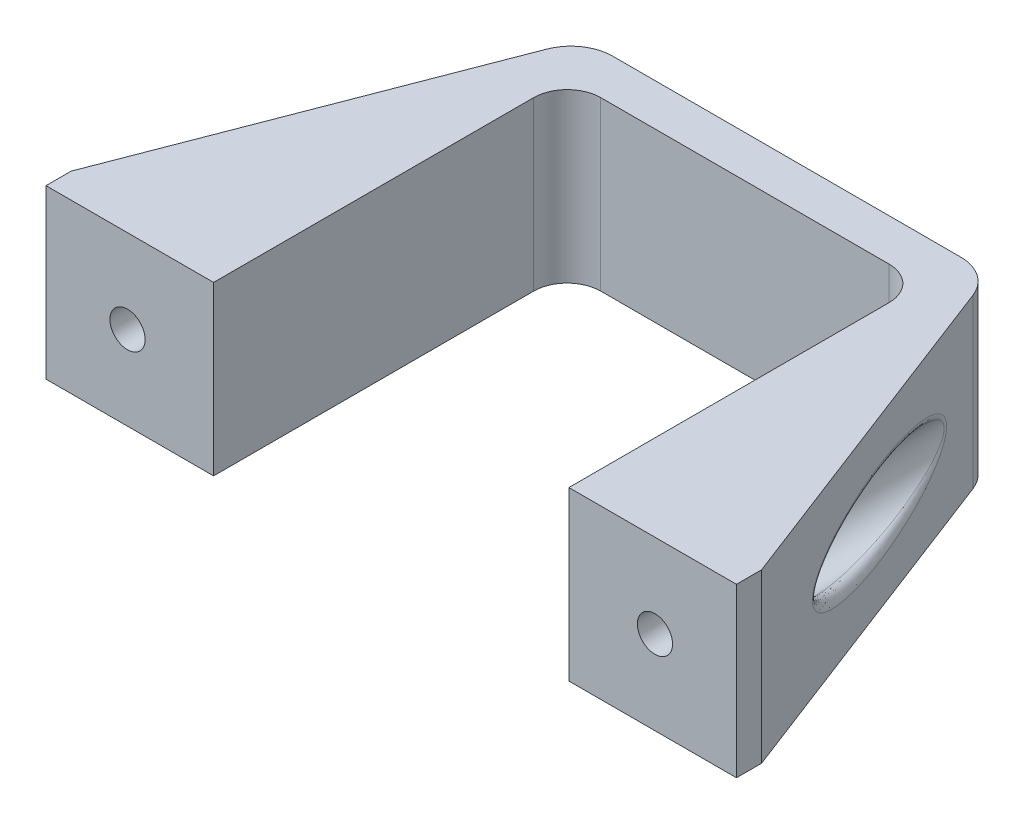
SolidWorks part; units mm, degrees
ref_plane "前视基准面" through (0, 0, 0) normal (0, 0, 1) x (1, 0, 0)
ref_plane "上视基准面" through (0, 0, 0) normal (0, 1, 0) x (1, 0, 0)
ref_plane "右视基准面" through (0, 0, 0) normal (1, 0, 0) x (0, 0, -1)
other "Configuration Table"
sketch "草图1" plane through (0, 0, 0) normal (0, 1, 0) x (1, 0, 0)
  line L0 (-21.2, 6.0133) -> (-21.2, 0)
  line L1 (-21.2, 42.2) -> (21.2, 42.2)
  line L2 (21.2, 42.2) -> (21.2, 6.0133)
  line L4 (41.2, 3) -> (41.2, 0)
  line L5 (41.2, 0) -> (21.2, 0)
  line L7 (0, 42.2) -> (0, 47.2)
  line L8 (-24.2, 47.2) -> (24.2, 47.2)
  line L10 (21.2, 6.0133) -> (21.2, 0)
  line L12 (-41.2, 0) -> (-21.2, 0)
  line L13 (-41.2, 3) -> (-41.2, 0)
  line L15 (-21.2, 42.2) -> (-21.2, 6.0133)
  line L16 (-24.2, 47.2) -> (-41.2, 3)
  line L17 (24.2, 47.2) -> (41.2, 3)
  dimension "D1" = 21.2
  dimension "D2" = 42.2
  dimension "D3" = 20
  dimension "D4" = 3
  dimension "D5" = 5
extrude "凸台-拉伸1" add sketch "草图1" along normal blind 20 contours L8 L17 L4 L5 L10 L2 L1 L15 L0 L12 L13 L16
fillet "圆角1" radius 5 2 edges at (-24.2, 10, -47.2) (24.2, 10, -47.2)
fillet "圆角2" radius 4 2 edges at (-21.2, 10, -42.2) (21.2, 10, -42.2)
sketch "草图2" plane through (0, 0, 0) normal (0, 0, 1) x (1, 0, 0)
  line L0 (0, 0) -> (0, 20) construction
  line L1 (-17.2, 20) -> (17.2, 20) construction
  circle A0 centre (-31.4723, 10) radius 2.1
  circle A1 centre (31.4723, 10) radius 2.1
  dimension "D1" = 4.2
extrude "切除-拉伸1" cut sketch "草图2" against normal blind 57
sketch "草图3" plane through (0, 0, -47.2) normal (0, 0, -1) x (-1, 0, 0)
  circle A0 centre (31.4723, 10) radius 4
  circle A1 centre (-31.4723, 10) radius 4
  dimension "D1" = 8
  dimension "D2" = 8
extrude "切除-拉伸2" cut sketch "草图3" against normal blind 44
fillet "圆角4" radius 1 2 edges at (-27.4723, 10, -38.6919) (27.4723, 10, -38.6919)
